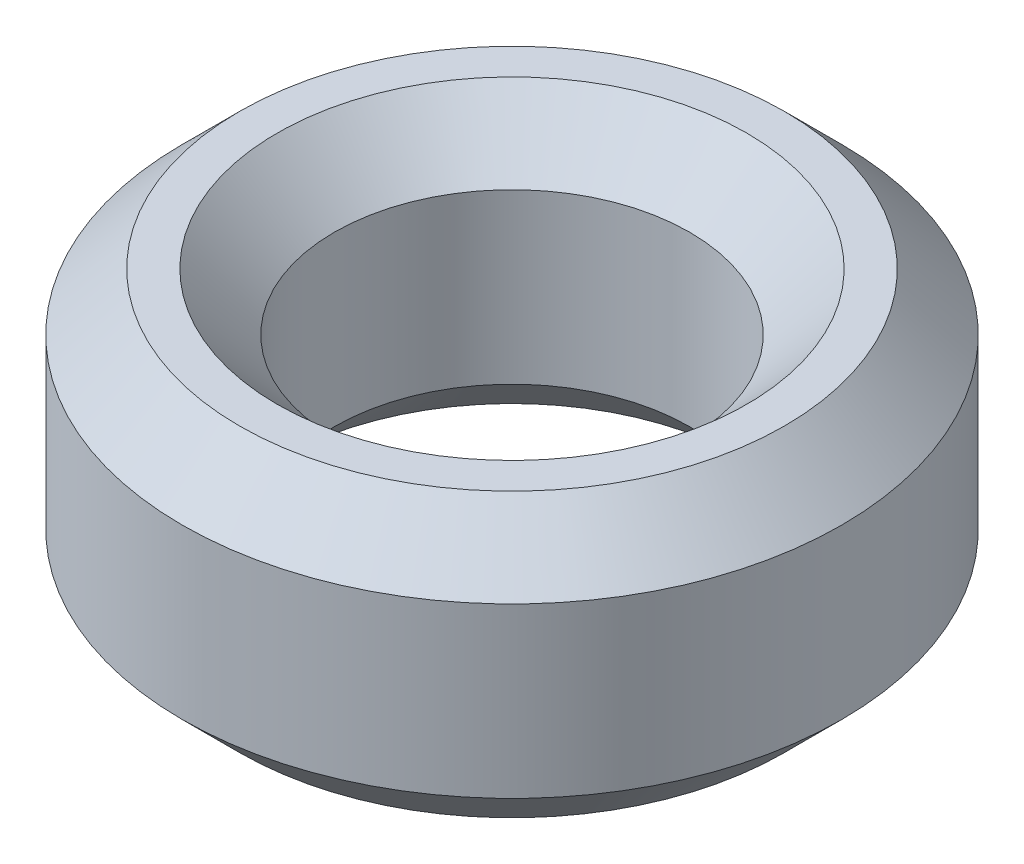
SolidWorks part; units mm, degrees
ref_plane "Front Plane" through (0, 0, 0) normal (0, 0, 1) x (1, 0, 0)
ref_plane "Top Plane" through (0, 0, 0) normal (0, 1, 0) x (1, 0, 0)
ref_plane "Right Plane" through (0, 0, 0) normal (1, 0, 0) x (0, 0, -1)
sketch "Sketch1" plane through (0, 0, 0) normal (0, 1, 0) x (1, 0, 0)
  circle A0 centre (0, 0) radius 22.5
  dimension "SLEEVE_OD" = 45
extrude "Boss-Extrude1" add sketch "Sketch1" along normal blind 19.3026
sketch "Sketch2" plane through (0, 0, 0) normal (0, 1, 0) x (1, 0, 0)
  circle A0 centre (0, 0) radius 12.1244
  dimension "BORE_D" = 24.2488
extrude "Cut-Extrude1" cut sketch "Sketch2" along normal through all
chamfer "Chamfer1" distance 3.9048 angle 45 4 edges at (0, 19.3026, 12.1244) (0, 0, 12.1244) (0, 0, 22.5) (0, 19.3026, 22.5)
